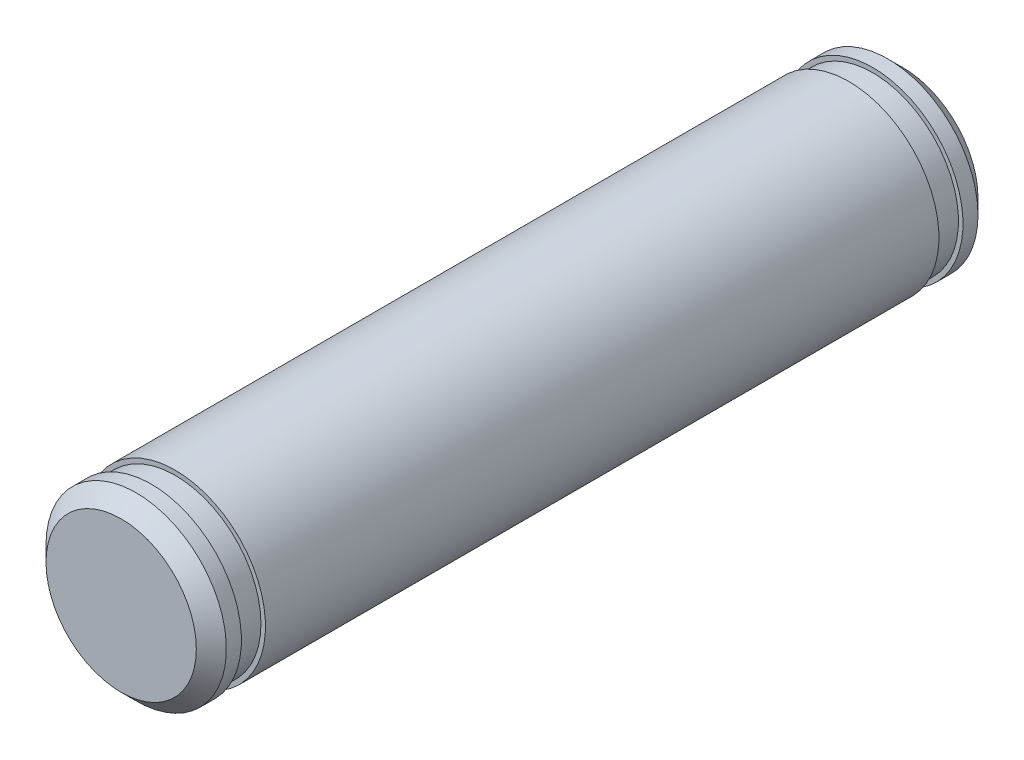
SolidWorks part; units mm, degrees
material "Stop 1060"
ref_plane "Płaszczyzna przednia" through (0, 0, 0) normal (0, 0, 1) x (1, 0, 0)
ref_plane "Płaszczyzna górna" through (0, 0, 0) normal (0, 1, 0) x (1, 0, 0)
ref_plane "Płaszczyzna prawa" through (0, 0, 0) normal (1, 0, 0) x (0, 0, -1)
sketch "Szkic1" plane through (0, 0, 0) normal (0, 0, 1) x (1, 0, 0)
  circle A0 centre (0, 0) radius 3
  dimension "D1" = 6
extrude "Dodanie-wyciągnięcie1" add sketch "Szkic1" along normal blind 26
chamfer "Sfazowanie1" distance 0.5 angle 45 2 edges at (3, 0, 0) (3, 0, 26)
sketch "Szkic2" plane through (0, 0, 26) normal (0, 0, 1) x (1, 0, 0)
  circle A0 centre (0, 0) radius 3
  circle A1 centre (0, 0) radius 2.85
  dimension "D1" = 6
  dimension "D2" = 5.7
extrude "Wytnij-wyciągnięcie1" cut sketch "Szkic2" against normal blind 0.8 from offset 1 offset against normal yes
sketch "Szkic3" plane through (0, 0, 0) normal (0, 0, -1) x (-1, 0, 0)
  circle A0 centre (0, 0) radius 2.85
  circle A1 centre (0, 0) radius 3
  dimension "D1" = 6
  dimension "D2" = 5.7
extrude "Wytnij-wyciągnięcie2" cut sketch "Szkic3" against normal blind 0.8 from offset 1 offset against normal yes
